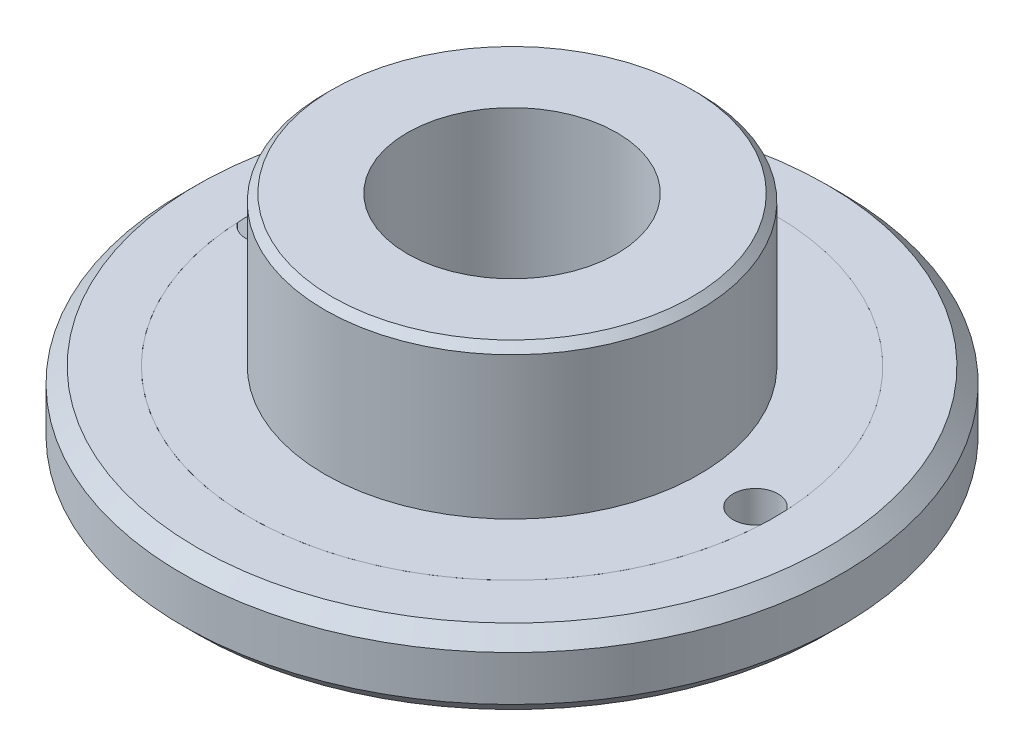
SolidWorks part; units mm, degrees
ref_plane "Front" through (0, 0, 0) normal (0, 0, 1) x (1, 0, 0)
ref_plane "Top" through (0, 0, 0) normal (0, 1, 0) x (1, 0, 0)
ref_plane "Right" through (0, 0, 0) normal (1, 0, 0) x (0, 0, -1)
sketch "Эскиз1" plane through (0, 0, 0) normal (0, 0, 1) x (1, 0, 0)
  line L0 (0, 0) -> (0, 6.9221) construction
  line L1 (7, 15) -> (7, 0)
  line L2 (7, 0) -> (17.5, 0)
  line L3 (17.5, 0) -> (17.5, 5)
  line L4 (17.5, 5) -> (12.5, 5)
  line L5 (12.5, 5) -> (12.5, 15)
  line L6 (12.5, 15) -> (7, 15)
  line L7 (0, 5) -> (0, 15) construction
  dimension "D1" = 35
  dimension "D2" = 14
  dimension "D3" = 5
  dimension "D5" = 25
revolve "Повернуть1" add sketch "Эскиз1" angle 360 about L0 region at (10.9709, 6.3372, 0)
sketch "Эскиз5" [suppressed] plane through (0, 0, 0) normal (0, 0, 1) x (1, 0, 0)
  line L0 (0, 0) -> (0, -50000) construction
  line L1 (-5, 0) -> (5, 0) construction
  line L2 (-5, 0) -> (5, 0) construction
  line L3 (11, 15) -> (-11, 15) construction
  line L4 (11, 15) -> (-11, 15) construction
  line L5 (5, 0) -> (5, -7.5)
  line L6 (5, -7.5) -> (11, -7.5)
  line L7 (11, -7.5) -> (11, 0)
  line L8 (11, 0) -> (5, 0)
  line L9 (6, -7.5) -> (-6, -7.5) construction
  line L10 (11, 15) -> (11, 15.5)
  line L11 (11, 15.5) -> (5, 15.5)
  line L12 (5, 15.5) -> (5, 15)
  line L13 (5, 15) -> (11, 15)
  line L14 (5, 15.5) -> (-5, 15.5) construction
ref_axis "Ось1" [suppressed] through (0, 15, 0) along (0, -1, 0)
revolve "Повернуть2" [suppressed] add sketch "Эскиз5" angle 360 about axis through (0, 15, 0) along (0, -1, 0)
sketch "Эскиз2" plane through (0, 0, 0) normal (0, 0, 1) x (1, 0, 0)
  line L3 (1.5, -27.4214) -> (-1.5, -27.4214)
  line L4 (1.5, -27.4214) -> (1.5, 27.4214)
  line L5 (1.5, 27.4214) -> (-1.5, 27.4214)
  line L6 (-1.5, -27.4214) -> (-1.5, 27.4214)
  line L7 (1.5, -27.4214) -> (-1.5, 27.4214) construction
  line L8 (1.5, 27.4214) -> (-1.5, -27.4214) construction
  point P0 (0, 0)
  dimension "D1" = 3
extrude "Вырез-Вытянуть1" [suppressed] cut sketch "Эскиз2" against normal blind 6.4
sketch "Эскиз3" plane through (0, 0, 0) normal (0, 0, 1) x (1, 0, 0)
  line L0 (0, 0) -> (0, 23.7771) construction
  line L1 (17.5, 0) -> (17.5, 5)
  line L2 (17.5, 0) -> (17.5, 5) construction
  line L3 (17.5, 5) -> (21, 5)
  line L6 (21, 5) -> (22, 4)
  line L7 (21, 0) -> (22, 1)
  line L8 (22, 1) -> (22, 4)
  line L11 (21, 0) -> (17.5, 0)
  line L12 (-17.5, 0) -> (17.5, 0) construction
  dimension "D1" = 45
  dimension "D2" = 1
  dimension "D3" = 44
revolve "Повернуть-Тонкостенный1" add sketch "Эскиз3" angle 360 about L0 wall 0.0001
sketch "Эскиз4" plane through (0, 5, 0) normal (0, 1, 0) x (1, 0, 0)
  circle A0 centre (-16.25, 0) radius 1.5
  circle A1 centre (16.25, 0) radius 1.5
  circle A2 centre (0, 0) radius 16.25 construction
  circle A3 centre (0, 0) radius 16.25 construction
  dimension "D3" = 3
extrude "Вырез-Вытянуть2" cut sketch "Эскиз4" against normal through all
chamfer "Фаска1" distance 0.5 angle 45 1 edges at (0, 15, -12.5)
